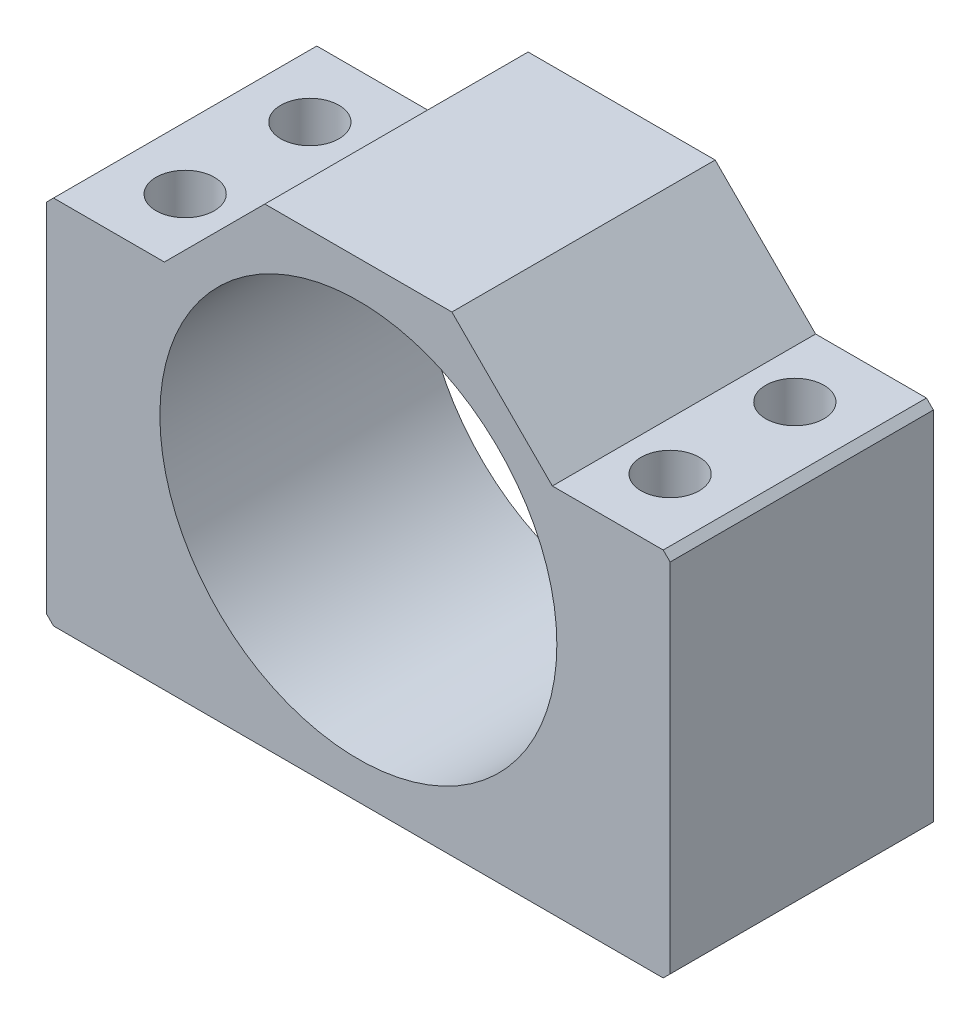
SolidWorks part; units mm, degrees
ref_plane "Front Plane" through (0, 0, 0) normal (0, 0, 1) x (1, 0, 0)
ref_plane "Top Plane" through (0, 0, 0) normal (0, 1, 0) x (1, 0, 0)
ref_plane "Right Plane" through (0, 0, 0) normal (1, 0, 0) x (0, 0, -1)
sketch "Sketch1" plane through (0, 0, 0) normal (0, 0, 1) x (1, 0, 0)
  line L1 (-45, -34) -> (45, -34)
  line L2 (-45, -34) -> (-45, 34)
  line L3 (-45, 34) -> (45, 34)
  line L4 (45, -34) -> (45, 34)
  line L5 (-45, -34) -> (45, 34) construction
  line L6 (-45, 34) -> (45, -34) construction
  circle A0 centre (0, 0) radius 28.65
  point P0 (0, 0)
  dimension "D3" = 57.3
  dimension "D1" = 90
  dimension "D2" = 68
extrude "Boss-Extrude1" add sketch "Sketch1" along normal mid plane 38
hole_wizard "M8 Clearance Hole1" positions "Sketch5" profile "Sketch4" hole size "M8" standard "ANSI Metric" end condition through all
sketch "Sketch5" plane through (0, 34, 0) normal (0, 1, 0) x (1, 0, 0)
  point P0 (-35, 9)
  point P2 (-35, -9)
  point P4 (35, -9)
  point P6 (35, 9)
  dimension "D1" = 35
  dimension "D2" = 9
  dimension "D3" = 35
  dimension "D4" = 9
  dimension "D5" = 35
  dimension "D6" = 9
  dimension "D7" = 35
  dimension "D8" = 9
sketch "Sketch4" plane through (-35, 34, -9) normal (1, 0, 0) x (0, 0, 1)
  line L0 (0, 0) -> (0, 68)
  line L1 (0, 68) -> (4.2, 68)
  line L2 (4.2, 68) -> (4.2, 0)
  line L5 (4.2, 0) -> (0, 0)
  line L11 (0, -6.35) -> (0, 107.95) construction
  dimension "Thru Hole Dia." = 8.4
  dimension "Thru Hole Depth" = 68
sketch "Sketch3" plane through (0, 0, 19) normal (0, 0, 1) x (1, 0, 0)
  line L0 (-45, 19.5) -> (-28, 19.5)
  line L1 (-45, 34) -> (-45, -34) construction
  line L2 (-28, 19.5) -> (-13.5, 34)
  line L3 (45, 34) -> (-45, 34) construction
  line L4 (-13.5, 34) -> (-45, 34)
  line L5 (-45, 34) -> (-45, 19.5)
  line L6 (-45, -34) -> (45, -34) construction
  line L7 (45, 19.5) -> (28, 19.5)
  line L8 (45, -34) -> (45, 34) construction
  line L9 (28, 19.5) -> (13.5, 34)
  line L10 (13.5, 34) -> (45, 34)
  line L11 (45, 34) -> (45, 19.5)
  dimension "D1" = 53.5
  dimension "D2" = 13.5
  dimension "D3" = 135
  dimension "D4" = 135
  dimension "D5" = 13.5
extrude "Cut-Extrude2" cut sketch "Sketch3" against normal through all
chamfer "Chamfer1" distance 1 angle 45 4 edges at (-45, 19.5, 0) (45, 19.5, 0) (45, -34, 0) (-45, -34, 0)
equation "\"D2@Sketch3\"=27/2"
equation "\"D5@Sketch3\"=\"D2@Sketch3\""
